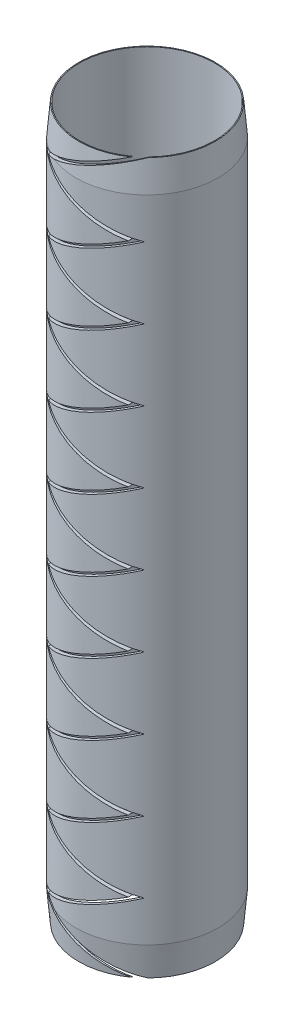
SolidWorks part; units mm, degrees
material "Plain Carbon Steel"
ref_plane "Front Plane" through (0, 0, 0) normal (0, 0, 1) x (1, 0, 0)
ref_plane "Top Plane" through (0, 0, 0) normal (0, 1, 0) x (1, 0, 0)
ref_plane "Right Plane" through (0, 0, 0) normal (1, 0, 0) x (0, 0, -1)
sketch "Sketch1" plane through (0, 0, 0) normal (0, 1, 0) x (1, 0, 0)
  circle A0 centre (0, 0) radius 1.016
  dimension "D1" = 2.032
extrude "Shaft" add sketch "Sketch1" along normal mid plane 10.16
ref_axis "Reference Axis" through (0, 5.08, 0) along (0, -1, 0)
shell "Shell" thickness 0.0508 removed face at (0, -5.08, 1.016) removed face at (0, 5.08, 1.016)
chamfer "Tip chamfer" distance 0.0381 angle 85 2 edges at (0, 5.08, 1.016) (0, -5.08, 1.016) first distance on face at (0, 5.08, 0.9652) first distance on face at (0, -5.08, 0.9652)
sketch "Sketch2" plane through (0, 0, 0) normal (0, 0, 1) x (1, 0, 0)
  line L0 (0, -5.08) -> (0, 5.08) construction
  line L1 (-0.9779, -5.08) -> (0.9779, -5.08) construction
  line L2 (0.9652, 5.08) -> (-0.9652, 5.08) construction
  line L3 (-0.635, 5.08) -> (-0.635, -5.08) construction
  line L4 (0.635, -5.08) -> (0.635, 5.08) construction
  line L5 (0.9779, 5.08) -> (-0.9779, 5.08) construction
  line L6 (-0.635, -0.4826) -> (0.5715, 0)
  line L7 (-0.635, -0.5334) -> (0.635, -0.0254)
  line L8 (0.635, -0.0254) -> (0.635, 0.0254) construction
  line L9 (-0.635, -0.5334) -> (-0.635, -0.4826) construction
  line L10 (-0.635, 0) -> (0.635, 0) construction
  line L11 (-0.635, 0.5334) -> (-0.635, 0.4826) construction
  line L12 (-0.635, 0.5334) -> (0.635, 0.0254)
  line L13 (-0.635, 0.4826) -> (0.5715, 0)
  line L14 (0.5715, 0) -> (0.635, 0.0254) construction
  line L15 (0.5715, 0) -> (0.635, -0.0254) construction
  line L16 (0.635, -0.0254) -> (0.6985, 0)
  line L17 (0.6985, 0) -> (0.635, 0.0254)
  line L18 (-0.635, -0.4826) -> (-0.6985, -0.508)
  line L19 (-0.6985, -0.508) -> (-0.635, -0.5334)
  line L20 (-0.635, 0.5334) -> (-0.6985, 0.508)
  line L21 (-0.6985, 0.508) -> (-0.635, 0.4826)
  point P15 (0.635, 0)
  point P22 (-0.635, -0.508)
  point P23 (-0.635, 0.508)
  dimension "D1" = 0.635
  dimension "D2" = 0.635
  dimension "D3" = 0.0508
  dimension "D4" = 0.0508
  dimension "D5" = 1.016
extrude "Zig zag cut" cut sketch "Sketch2" along normal blind 3.3495
pattern_linear "Linear pattern for zig zag cut" count 6 spacing 1.016 along (0, -1, 0) count 6 spacing 1.016 along (0, 1, 0) of "Zig zag cut" pattern seed only yes
equation "\"D4@Sketch2\"=\"D3@Sketch2\""
equation "\"D5@Sketch2\"=\"pinLength@Shaft\"/10"
equation "\"D3@Linear pattern for zig zag cut\"=\"pinLength@Shaft\"/10"
equation "\"D4@Linear pattern for zig zag cut\"=\"pinLength@Shaft\"/10"
equation "\"D2@Sketch2\"=\"D1@Sketch2\""
